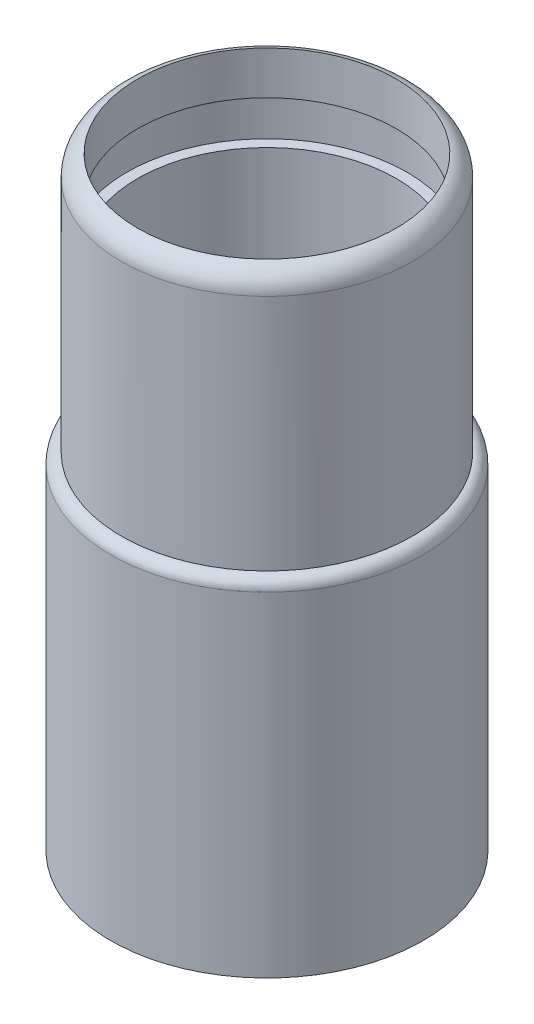
SolidWorks part; units mm, degrees
ref_plane "Front Plane" through (0, 0, 0) normal (0, 0, 1) x (1, 0, 0)
ref_plane "Top Plane" through (0, 0, 0) normal (0, 1, 0) x (1, 0, 0)
ref_plane "Right Plane" through (0, 0, 0) normal (1, 0, 0) x (0, 0, -1)
sketch "Sketch1" plane through (0, 0, 0) normal (0, 1, 0) x (1, 0, 0)
  circle A0 centre (0, 0) radius 3
  circle A1 centre (0, 0) radius 3.375
  dimension "D1" = 6
  dimension "D2" = 6.75
extrude "Boss-Extrude1" add sketch "Sketch1" along normal blind 14
sketch "Sketch2" plane through (0, 0, 0) normal (0, -1, 0) x (1, 0, 0)
  circle A0 centre (0, 0) radius 3.625
  circle A1 centre (0, 0) radius 3.375 construction
  circle A2 centre (0, 0) radius 3 construction
  circle A3 centre (0, 0) radius 3
  dimension "D1" = 0.25
extrude "Boss-Extrude2" add sketch "Sketch2" against normal blind 8
fillet "Fillet1" radius 0.25 1 edges at (0, 8, -3.625)
sketch "Sketch3" plane through (0, 14, 0) normal (0, 1, 0) x (1, 0, 0)
  circle A0 centre (0, 0) radius 3.375 construction
  circle A1 centre (0, 0) radius 3
  circle A2 centre (0, 0) radius 3.375
  dimension "D1" = 6
extrude "Boss-Extrude3" add sketch "Sketch3" against normal blind 0.5
fillet "Fillet2" radius 0.5 1 edges at (0, 14, 3.375)
sketch "Sketch4" plane through (0, 0, 0) normal (0, -1, 0) x (1, 0, 0)
  circle A0 centre (0, 0) radius 3.25
  dimension "D1" = 6.5
extrude "Cut-Extrude1" cut sketch "Sketch4" against normal blind 4
ref_plane "Plane1" through (0, 12, 0) normal (0, -1, 0) x (-1, 0, 0)
sketch "Sketch5" plane through (0, 12, 0) normal (0, -1, 0) x (-1, 0, 0)
  circle A0 centre (0, 0) radius 3.25 construction
  circle A1 centre (0, 0) radius 3.25
extrude "Cut-Extrude2" cut sketch "Sketch5" against normal blind 1
